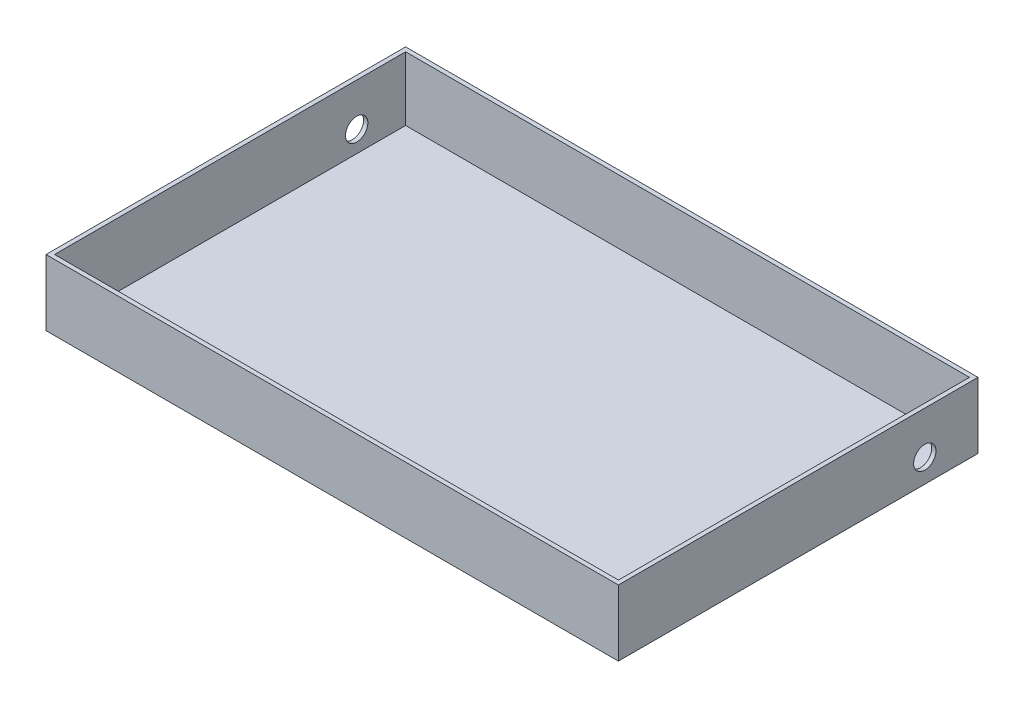
SolidWorks part; units mm, degrees
ref_plane "Front Plane" through (0, 0, 0) normal (0, 0, 1) x (1, 0, 0)
ref_plane "Top Plane" through (0, 0, 0) normal (0, 1, 0) x (1, 0, 0)
ref_plane "Right Plane" through (0, 0, 0) normal (1, 0, 0) x (0, 0, -1)
sketch "Sketch2" plane through (0, 0, 0) normal (0, 1, 0) x (1, 0, 0)
  line L0 (64.0061, 46.7958) -> (64.0061, -118.2042) construction
  line L1 (-68.4939, 46.7958) -> (196.5061, 46.7958)
  line L2 (-68.4939, 46.7958) -> (-68.4939, -118.2042)
  line L3 (-68.4939, -118.2042) -> (196.5061, -118.2042)
  line L4 (196.5061, 46.7958) -> (196.5061, -118.2042)
  line L5 (-68.4939, -35.7042) -> (196.5061, -35.7042) construction
  line L7 (-70.4939, 48.7958) -> (198.5061, 48.7958)
  line L8 (-70.4939, 48.7958) -> (-70.4939, -120.2042)
  line L9 (-70.4939, -120.2042) -> (198.5061, -120.2042)
  line L10 (198.5061, 48.7958) -> (198.5061, -120.2042)
  dimension "D1" = 165
  dimension "D2" = 265
  dimension "D3" = 2
  dimension "D4" = 2
  dimension "D5" = 2
  dimension "D6" = 2
extrude "Walls" add sketch "Sketch2" along normal blind 30
extrude "Base" add sketch "Sketch2<2>" against normal blind 1 contours L4 L1 L2 L3 | L10 L7 L8 L9 L1 L4 L3 L2 region at (64.0061, 0, 35.7042) region at (64.0061, 0, -48.4781)
sketch "Sketch2<2>" plane through (0, 0, 0) normal (0, 1, 0) x (1, 0, 0) same geometry as "Sketch2"
sketch "Sketch3" plane through (-70.4939, 0, 0) normal (-1, 0, 0) x (0, 0, 1)
  line L0 (35.7042, 30) -> (35.7042, -1) construction
  line L1 (-48.7958, 30) -> (120.2042, 30) construction
  line L3 (-23.7958, 30) -> (-23.7958, -1.8082) construction
  line L4 (-48.7958, 30) -> (-48.7958, -1) construction
  line L5 (-48.7958, -1) -> (120.2042, -1) construction
  circle A0 centre (-23.7958, 10) radius 5.25
  point P12 (-23.7958, 10)
  dimension "D1" = 10.5
  dimension "D2" = 11
  dimension "D3" = 25
sketch "Sketch4" plane through (198.5061, 0, 0) normal (1, 0, 0) x (0, 0, -1)
  line L0 (-35.7042, 30) -> (-35.7042, -1) construction
  line L1 (23.7958, 30) -> (23.7958, -1) construction
  line L2 (48.7958, 30) -> (48.7958, -1) construction
  line L3 (-120.2042, 30) -> (48.7958, 30) construction
  line L5 (48.7958, -1) -> (-120.2042, -1) construction
  circle A0 centre (23.7958, 10) radius 5.25
  point P12 (-35.7042, 10)
  point P13 (23.7958, 10)
  dimension "D1" = 10.5
  dimension "D2" = 11
  dimension "D3" = 25
extrude "Motor-Wheel" cut sketch "Sketch4" against normal blind 10
extrude "Motor-Wheel2" cut sketch "Sketch3" against normal blind 10
sketch "Sketch6" plane through (0, 0, 0) normal (0, 1, 0) x (1, 0, 0)
  line L0 (-70.4939, 48.7958) -> (-70.4939, -120.2042) construction
  line L1 (-70.4939, -120.2042) -> (198.5061, -120.2042) construction
  line L2 (64.0061, -118.2042) -> (64.0061, 46.7958) construction
  circle A0 centre (-45.4939, -95.2042) radius 3.35
  circle A1 centre (173.5061, -95.2042) radius 3.35
  dimension "D1" = 6.7
  dimension "D2" = 25
  dimension "D3" = 25
extrude "Caster Wheels" cut sketch "Sketch6" against normal blind 10
sketch "CamSlip" plane through (0, 0, 120.2042) normal (0, 0, 1) x (1, 0, 0)
  line L0 (64.0061, 30) -> (64.0061, -1) construction
  line L1 (-70.4939, 30) -> (198.5061, 30) construction
  line L2 (-70.4939, -1) -> (198.5061, -1) construction
  line L3 (64.0061, 30) -> (64.0061, 29.7) construction
  line L4 (55.7561, 30) -> (72.2561, 30)
  line L5 (55.7561, 30) -> (55.7561, 29.7)
  line L6 (55.7561, 29.7) -> (72.2561, 29.7)
  line L7 (72.2561, 30) -> (72.2561, 29.7)
  dimension "D1" = 0.3
  dimension "D2" = 16.5
